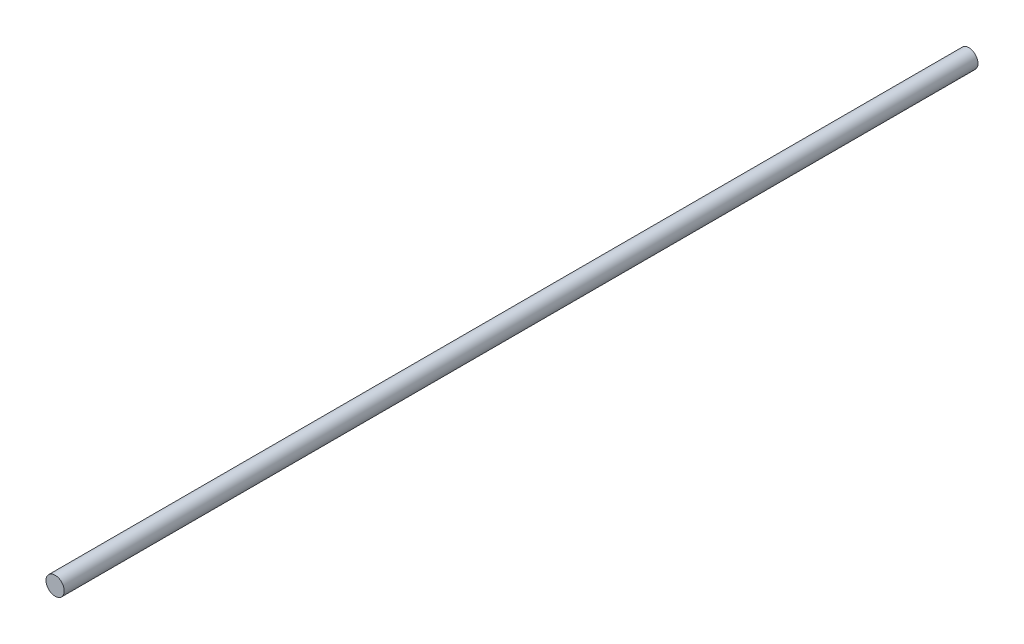
SolidWorks part; units mm, degrees
ref_plane "Front Plane" through (0, 0, 0) normal (0, 0, 1) x (1, 0, 0)
ref_plane "Top Plane" through (0, 0, 0) normal (0, 1, 0) x (1, 0, 0)
ref_plane "Right Plane" through (0, 0, 0) normal (1, 0, 0) x (0, 0, -1)
sketch "Sketch1" plane through (0, 0, 0) normal (0, 0, 1) x (1, 0, 0)
  circle A0 centre (0, 0) radius 4
  dimension "D1" = 8
extrude "Boss-Extrude1" add sketch "Sketch1" against normal blind 400
ref_axis "Axis1" through (0, 0, -400) along (0, 0, 1)
